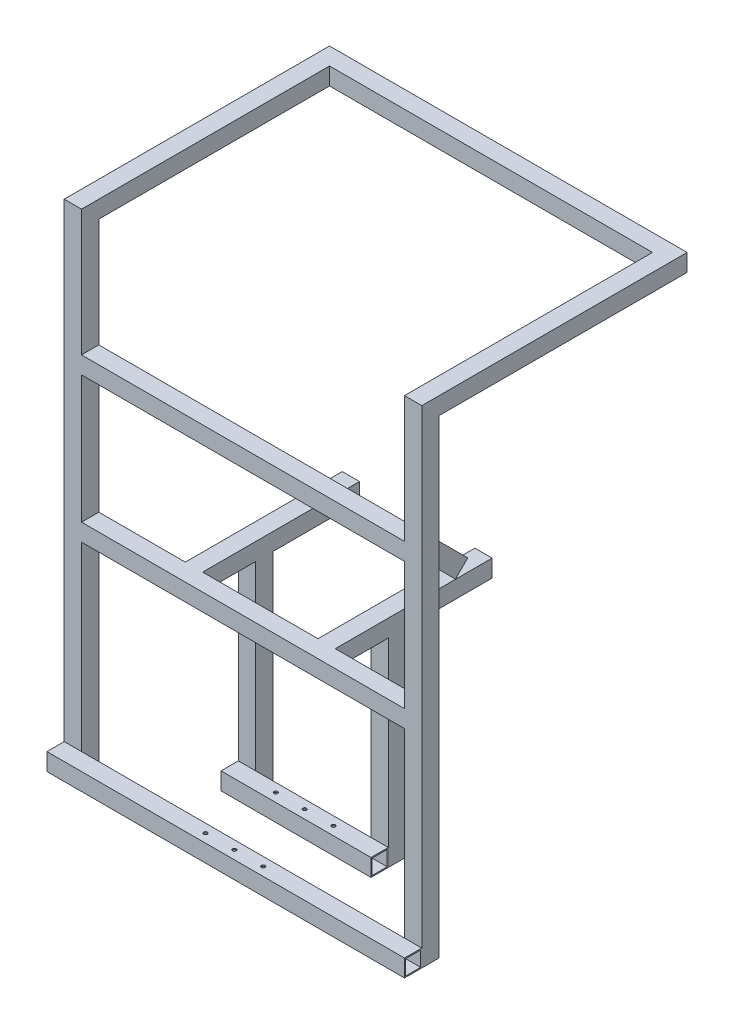
SolidWorks part; units mm, degrees
material "6061 合金"
ref_plane "前视基准面" through (0, 0, 0) normal (0, 0, 1) x (1, 0, 0)
ref_plane "上视基准面" through (0, 0, 0) normal (0, 1, 0) x (1, 0, 0)
ref_plane "右视基准面" through (0, 0, 0) normal (1, 0, 0) x (0, 0, -1)
ref_plane "基准面1" through (0, 290, 0) normal (0, 1, 0) x (1, 0, 0)
ref_axis "基准轴1" through (93.0057, 290, 0) along (-1, 0, 0)
ref_plane "基准面2" through (0, 145, -145) normal (0, 0.7071, -0.7071) x (-1, 0, 0)
sketch "草图1" plane through (0, 0, 0) normal (0, 1, 0) x (1, 0, 0)
  line L1 (-65, 38) -> (-50, 38)
  line L2 (-65, 38) -> (-65, 23)
  line L3 (-65, 23) -> (-50, 23)
  line L4 (-50, 38) -> (-50, 23)
  line L5 (-64, 37) -> (-51, 37)
  line L6 (-64, 37) -> (-64, 24)
  line L7 (-64, 24) -> (-51, 24)
  line L8 (-51, 37) -> (-51, 24)
  line L32 (93.0057, 0) -> (-84.9743, 0) construction
  line L33 (0, 0) -> (0, 38.615) construction
  line L34 (0, 0) -> (-50.2989, 0) construction
  line L35 (51, 37) -> (51, 24)
  line L36 (64, 24) -> (51, 24)
  line L37 (64, 37) -> (64, 24)
  line L38 (64, 37) -> (51, 37)
  line L39 (50, 38) -> (50, 23)
  line L40 (65, 23) -> (50, 23)
  line L41 (65, 38) -> (65, 23)
  line L42 (65, 38) -> (50, 38)
  line L59 (141, -24) -> (141, -37)
  line L60 (-155, -23) -> (-140, -23)
  line L61 (-155, -23) -> (-155, -38)
  line L62 (-155, -38) -> (-140, -38)
  line L63 (-140, -23) -> (-140, -38)
  line L64 (-154, -24) -> (-141, -24)
  line L65 (-154, -24) -> (-154, -37)
  line L66 (-154, -37) -> (-141, -37)
  line L67 (-141, -24) -> (-141, -37)
  line L68 (154, -37) -> (141, -37)
  line L69 (154, -24) -> (154, -37)
  line L70 (154, -24) -> (141, -24)
  line L71 (140, -23) -> (140, -38)
  line L72 (155, -38) -> (140, -38)
  line L73 (155, -23) -> (155, -38)
  line L74 (155, -23) -> (140, -23)
  dimension "D1" = 15
  dimension "D2" = 13
  dimension "D3" = 13
  dimension "D4" = 1
  dimension "D5" = 1
  dimension "D6" = 50
  dimension "D7" = 1
  dimension "D8" = 1
  dimension "D9" = 13
  dimension "D10" = 1
  dimension "D11" = 1
  dimension "D12" = 13
  dimension "D13" = 23
  dimension "D14" = 140
  dimension "D16" = 23
extrude "凸台-拉伸1" add sketch "草图1" along normal up to surface (252 mm away) up to plane "基准面2"
ref_plane "基准面3" through (0, 107, 107) normal (0, -0.7071, -0.7071) x (-1, 0, 0)
ref_plane "基准面4" through (65, 0, -38) normal (0, -1, 0) x (-1, 0, 0)
sketch "草图2" plane through (-65, 0, 0) normal (-1, 0, 0) x (0, 0, 1)
  line L0 (-118, 0) -> (-8, 0) construction
  line L1 (-22.9885, 0) -> (-7.9885, 0)
  line L2 (-22.9885, 0) -> (-22.9885, 15)
  line L3 (-22.9885, 15) -> (-7.9885, 15)
  line L4 (-7.9885, 0) -> (-7.9885, 15)
  line L6 (-21.9885, 1) -> (-8.9885, 1)
  line L7 (-21.9885, 1) -> (-21.9885, 14)
  line L8 (-21.9885, 14) -> (-8.9885, 14)
  line L9 (-8.9885, 1) -> (-8.9885, 14)
  dimension "D1" = 15
  dimension "D2" = 15
  dimension "D3" = 1
  dimension "D4" = 1
  dimension "D5" = 1
  dimension "D6" = 1
extrude "凸台-拉伸2" add sketch "草图2" against normal up to vertex (130 mm away) separate body up to point (65, 0, -23)
sketch "草图3" plane through (-155, 0, 0) normal (-1, 0, 0) x (0, 0, 1)
  line L1 (38, 0) -> (53, 0)
  line L2 (38, 0) -> (38, 15)
  line L3 (38, 15) -> (53, 15)
  line L4 (53, 0) -> (53, 15)
  line L5 (39, 1) -> (52, 1)
  line L6 (39, 1) -> (39, 14)
  line L7 (39, 14) -> (52, 14)
  line L8 (52, 1) -> (52, 14)
  dimension "D1" = 15
  dimension "D2" = 15
  dimension "D3" = 1
  dimension "D4" = 1
  dimension "D5" = 1
  dimension "D6" = 1
extrude "凸台-拉伸3" add sketch "草图3" against normal up to vertex (310 mm away) up to point (155, 0, 38)
sketch "草图4" plane through (0, 15, 0) normal (0, 1, 0) x (1, 0, 0)
  circle A0 centre (-25, -45.5) radius 1.6 construction
  circle A1 centre (0, -45.5) radius 1.6 construction
  circle A2 centre (25, -45.5) radius 1.6 construction
  circle A3 centre (-25, 15.4745) radius 1.6 construction
  circle A4 centre (0, 15.4745) radius 1.6 construction
  circle A5 centre (25, 15.5) radius 1.6 construction
  circle A6 centre (-25, -45.5) radius 1.6
  circle A7 centre (0, -45.5) radius 1.6
  circle A8 centre (25, -45.5) radius 1.6
  circle A9 centre (-25, 15.4745) radius 1.6
  circle A10 centre (0, 15.4745) radius 1.6
  circle A11 centre (25, 15.5) radius 1.6
extrude "切除-拉伸1" cut sketch "草图4" against normal blind 15
sketch "草图5" plane through (0, 0, -23) normal (0, 0, 1) x (1, 0, 0)
  line L1 (50, 187.2397) -> (65, 187.2397)
  line L2 (50, 187.2397) -> (50, 172.2397)
  line L3 (50, 172.2397) -> (65, 172.2397)
  line L4 (65, 187.2397) -> (65, 172.2397)
  line L5 (-50, 179.7397) -> (50, 179.7397) construction
  line L6 (51, 186.2397) -> (64, 186.2397)
  line L7 (51, 186.2397) -> (51, 173.2397)
  line L8 (51, 173.2397) -> (64, 173.2397)
  line L9 (64, 186.2397) -> (64, 173.2397)
  line L10 (-50, 252) -> (-50, 0) construction
  line L11 (50, 252) -> (50, 0) construction
  line L12 (50, 179.7397) -> (0, 179.7397)
  line L13 (0, 179.7397) -> (0, 199.5697) construction
  line L14 (-64, 186.2397) -> (-64, 173.2397)
  line L15 (-51, 173.2397) -> (-64, 173.2397)
  line L16 (-51, 186.2397) -> (-51, 173.2397)
  line L17 (-51, 186.2397) -> (-64, 186.2397)
  line L18 (-65, 187.2397) -> (-65, 172.2397)
  line L19 (-50, 172.2397) -> (-65, 172.2397)
  line L20 (-50, 187.2397) -> (-50, 172.2397)
  line L21 (-50, 187.2397) -> (-65, 187.2397)
  ellipse E0 centre (0, 282.7279) end of major axis (144, 282.7279) minor radius 101.8234 construction
  point P8 (50, 179.7397)
  dimension "D1" = 15
  dimension "D2" = 15
  dimension "D3" = 1
  dimension "D4" = 13
  dimension "D5" = 1
  dimension "D6" = 13
extrude "凸台-拉伸4" add sketch "草图5" against normal blind 90 and the other way up to vertex (46 mm away) contours L9 L6 L7 L8 | L2 L3 L4 L1 | L16 L15 L14 L17 | L18 L19 L20 L21 region at (57.5, 179.7397, -23) other way up to point (-140, 0, 23)
sketch "草图6" plane through (-140, 0, 0) normal (1, 0, 0) x (0, 0, -1)
  line L0 (-38, 328) -> (-38, 15) construction
  line L1 (-23, 187.2397) -> (-38, 187.2397)
  line L2 (-23, 187.2397) -> (-23, 172.2397)
  line L3 (-23, 172.2397) -> (-38, 172.2397)
  line L4 (-38, 187.2397) -> (-38, 172.2397)
  line L6 (-24, 186.2397) -> (-37, 186.2397)
  line L7 (-24, 186.2397) -> (-24, 173.2397)
  line L8 (-24, 173.2397) -> (-37, 173.2397)
  line L9 (-37, 186.2397) -> (-37, 173.2397)
  dimension "D1" = 1
  dimension "D2" = 13
  dimension "D3" = 1
  dimension "D4" = 13
extrude "凸台-拉伸5" add sketch "草图6" along normal up to vertex (280 mm away) up to point (140, 15, 38)
ref_plane "基准面5" through (0, 407.2397, 0) normal (0, 1, 0) x (1, 0, 0)
sketch "草图7" plane through (0, 407.2397, 0) normal (0, 1, 0) x (1, 0, 0)
  line L0 (-140, -23) -> (-140, -38)
  line L1 (-155, 192) -> (155, 192)
  line L2 (-155, 192) -> (-155, -38)
  line L4 (155, 192) -> (155, -38)
  line L5 (-140, 177) -> (140, 177)
  line L6 (-140, 177) -> (-140, -23)
  line L8 (140, 177) -> (140, -23)
  line L9 (-65, -23) -> (-65, 23) construction
  line L10 (65, -23) -> (65, 23) construction
  line L12 (140, -23) -> (140, -38)
  line L13 (140, -38) -> (155, -38)
  line L14 (-155, -38) -> (-140, -38)
  line L15 (155, -38) -> (140, -38) construction
  line L16 (-155, -38) -> (-140, -38) construction
  line L17 (140, -38) -> (155, -38) construction
  dimension "D1" = 90
  dimension "D2" = 90
  dimension "D3" = 15
  dimension "D4" = 15
  dimension "D5" = 15
  dimension "D6" = 230
extrude "凸台-拉伸6" add sketch "草图7" along normal blind 15 separate body
sketch "草图8" plane through (0, 407.2397, 0) normal (0, -1, 0) x (1, 0, 0)
  line L0 (155, 38) -> (155, 23) construction
  line L1 (155, 23) -> (140, 23) construction
  line L2 (140, 23) -> (140, 38) construction
  line L3 (140, 38) -> (155, 38) construction
  line L4 (-155, 38) -> (-155, -192) construction
  line L5 (-155, -192) -> (155, -192) construction
  line L7 (-140, 38) -> (-155, 38) construction
  line L8 (141, 37) -> (154, 37) construction
  line L9 (155, 38) -> (155, 23)
  line L10 (155, 23) -> (140, 23)
  line L11 (140, 23) -> (140, 38)
  line L12 (140, 38) -> (155, 38)
  line L13 (-155, 38) -> (-155, -192)
  line L14 (-155, -192) -> (155, -192)
  line L15 (155, -192) -> (-140, 38)
  line L16 (-140, 38) -> (-155, 38)
  line L17 (141, 37) -> (154, 37)
  line L18 (141, 24) -> (141, 37) construction
  line L19 (154, 24) -> (141, 24) construction
  line L20 (154, 37) -> (154, 24) construction
  line L21 (141, 24) -> (141, 37)
  line L22 (154, 24) -> (141, 24)
  line L23 (154, 37) -> (154, 24)
  line L24 (-155, 23) -> (-155, 38) construction
  line L25 (-154, 24) -> (-154, 37) construction
  line L26 (-155, 38) -> (-140, 38) construction
  line L27 (-154, 37) -> (-141, 37) construction
  line L28 (-141, 24) -> (-154, 24) construction
  line L29 (-140, 23) -> (-155, 23) construction
  line L30 (-141, 37) -> (-141, 24) construction
  line L31 (-140, 38) -> (-140, 23) construction
  line L32 (-155, 23) -> (-155, 38)
  line L33 (-154, 24) -> (-154, 37)
  line L34 (-155, 38) -> (-140, 38)
  line L35 (-154, 37) -> (-141, 37)
  line L36 (-141, 24) -> (-154, 24)
  line L37 (-140, 23) -> (-155, 23)
  line L38 (-141, 37) -> (-141, 24)
  line L39 (-140, 38) -> (-140, 23)
  line M4 (-140, 38) -> (-155, 38)
extrude "凸台-拉伸7" add sketch "草图8" along normal up to surface (93.2397 mm away) contours L39 L16 L32 L35 L38 L36 L33 | L11 L9 L17 L23 L22 L21 M4 region at (154.7879, 407.2397, 30.5) region at (-147.5, 407.2397, 37.7879) up to face at (147.5, 320.5, 30.5)
sketch "草图10" plane through (140, 0, 0) normal (-1, 0, 0) x (0, 0, 1)
  line L0 (23, 407.2397) -> (23, 0) construction
  line L1 (23, 312.8277) -> (38, 312.8277)
  line L2 (23, 312.8277) -> (23, 297.8277)
  line L3 (23, 297.8277) -> (38, 297.8277)
  line L4 (38, 312.8277) -> (38, 297.8277)
  line L5 (38, 422.2397) -> (38, 15) construction
  dimension "D1" = 15
extrude "凸台-拉伸9" add sketch "草图10" along normal up to vertex (280 mm away) up to point (-140, 15, 38)
sketch "草图11" plane through (65, 0, 0) normal (1, 0, 0) x (0, 0, -1)
  line L1 (23, 187.2397) -> (70.4156, 187.2397)
  line L2 (23, 187.2397) -> (23, 273.1063)
  line L3 (23, 273.1063) -> (70.4156, 273.1063)
  line L4 (70.4156, 187.2397) -> (70.4156, 273.1063)
extrude "切除-拉伸2" cut sketch "草图11" against normal blind 251
ref_plane "基准面6" through (0, 145, 145) normal (0, -0.7071, -0.7071) x (-1, 0, 0)
sketch "草图12" plane through (0, 145, 145) normal (0, -0.7071, -0.7071) x (-1, 0, 0)
  line L0 (-65, 212.3015) -> (-65, 201.6949) construction
  line L1 (-65, 204.9391) -> (-50, 204.9391)
  line L2 (-65, 204.9391) -> (-65, 189.9391)
  line L3 (-65, 189.9391) -> (-50, 189.9391)
  line L4 (-50, 204.9391) -> (-50, 189.9391)
  line L5 (-50, 148.6619) -> (-50, 201.6949) construction
  line L6 (65, 212.3015) -> (65, 201.6949) construction
  line L7 (65, 204.9391) -> (50, 204.9391)
  line L8 (65, 204.9391) -> (65, 189.9391)
  line L9 (65, 189.9391) -> (50, 189.9391)
  line L10 (50, 204.9391) -> (50, 189.9391)
  line L11 (50, 148.6619) -> (50, 201.6949) construction
  line L12 (140, 204.9391) -> (-140, 204.9391) construction
  line L14 (-64, 190.9391) -> (-51, 190.9391)
  line L15 (-64, 190.9391) -> (-64, 203.9391)
  line L16 (-64, 203.9391) -> (-51, 203.9391)
  line L17 (-51, 190.9391) -> (-51, 203.9391)
  line L18 (51, 203.9391) -> (64, 203.9391)
  line L19 (51, 203.9391) -> (51, 190.9391)
  line L20 (51, 190.9391) -> (64, 190.9391)
  line L21 (64, 203.9391) -> (64, 190.9391)
  dimension "D1" = 15
  dimension "D2" = 15
  dimension "D3" = 1
  dimension "D4" = 1
  dimension "D5" = 1
  dimension "D6" = 1
  dimension "D7" = 1
  dimension "D8" = 1
  dimension "D9" = 1
  dimension "D10" = 1
extrude "凸台-拉伸10" add sketch "草图12" along normal blind 130 and the other way up to vertex (32.4051 mm away) other way up to point (-140, 312.8277, 23)
sketch "草图13" plane through (0, 134.3072, -134.3072) normal (0, -0.7071, 0.7071) x (1, 0, 0)
  line L0 (-50, 175.3624) -> (50, 175.3624) construction
  line L1 (-50, 231.2528) -> (-50, 75.061) construction
  line L2 (50, 231.2528) -> (50, 75.061) construction
  line L3 (0, 175.3624) -> (0, 183.6735) construction
  line L4 (-57.5, 202.3742) -> (-57.5, 105.061) construction
  line L5 (-50, 75.061) -> (-65, 75.061) construction
  line L6 (-65, 231.2528) -> (-65, 75.061) construction
  line L7 (57.5, 202.3742) -> (57.5, 105.061) construction
  circle A0 centre (-57.5, 185.061) radius 1.6
  circle A1 centre (-57.5, 165.061) radius 1.6
  circle A2 centre (-57.5, 145.061) radius 1.6
  circle A3 centre (-57.5, 125.061) radius 1.6
  circle A4 centre (-57.5, 105.061) radius 1.6
  circle A5 centre (57.5, 105.061) radius 1.6
  circle A6 centre (57.5, 125.061) radius 1.6
  circle A7 centre (57.5, 145.061) radius 1.6
  circle A8 centre (57.5, 165.061) radius 1.6
  circle A9 centre (57.5, 185.061) radius 1.6
  dimension "D1" = 3.2
  dimension "D2" = 20
  dimension "D3" = 20
  dimension "D4" = 3.2
  dimension "D5" = 20
  dimension "D6" = 50
  dimension "D8" = 3.2
  dimension "D9" = 20
  dimension "D7" = 7.5
extrude "切除-拉伸3" cut sketch "草图13" against normal blind 66
